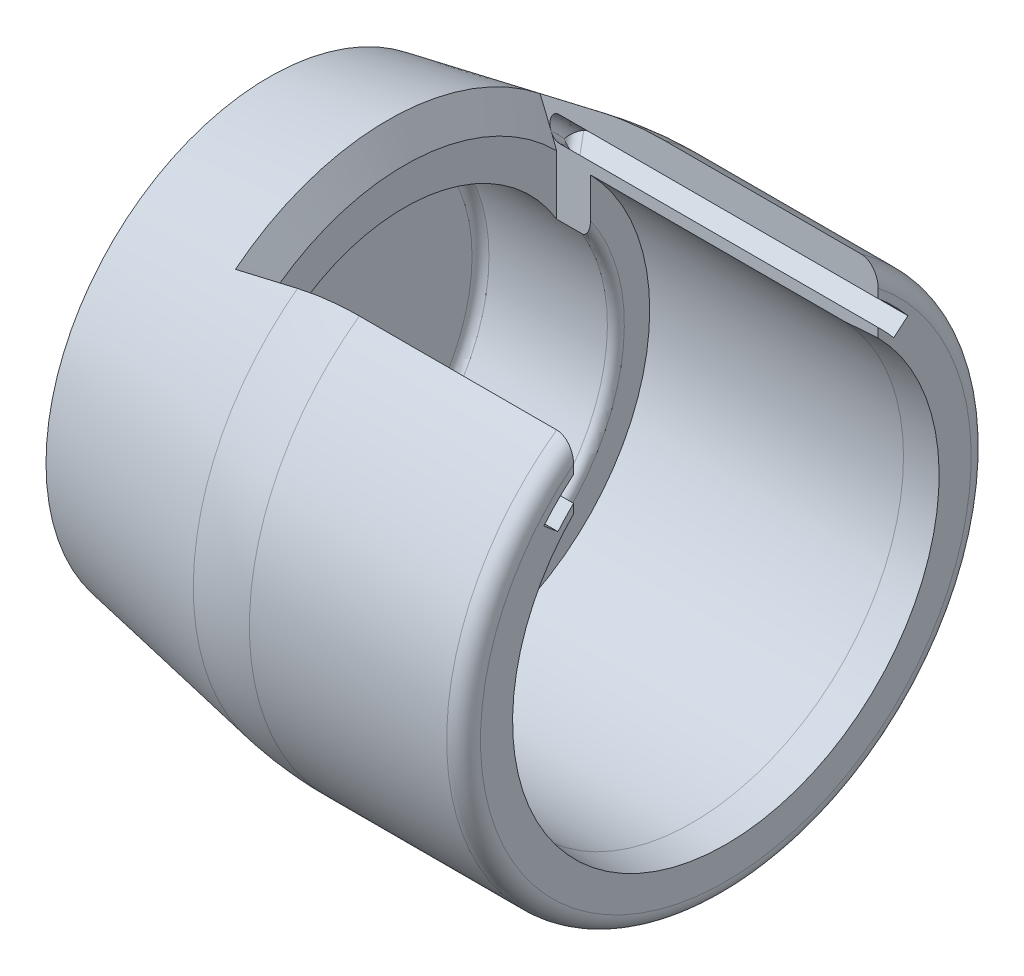
SolidWorks part; units mm, degrees
material "ABS"
ref_plane "Přední rovina" through (0, 0, 0) normal (0, 0, 1) x (1, 0, 0)
ref_plane "Horní rovina" through (0, 0, 0) normal (0, 1, 0) x (1, 0, 0)
ref_plane "Pravá rovina" through (0, 0, 0) normal (1, 0, 0) x (0, 0, -1)
sketch "Skica1" plane through (0, 0, 0) normal (0, 0, 1) x (1, 0, 0)
  line L0 (-22.0025, 0) -> (25.5285, 0) construction
  line L1 (-18.0063, 0) -> (-18.0063, 15.5)
  line L2 (-18.0063, 15.5) -> (8.9937, 15.5)
  line L3 (9.9937, 14.5) -> (9.9937, 12.5)
  line L4 (9.9937, 12.5) -> (-7.0063, 12.5)
  line L5 (-15.0063, 10.5) -> (-15.0063, 0)
  line L6 (-15.0063, 0) -> (-18.0063, 0)
  line L7 (-18.0063, 12.9944) -> (-4.5063, 15.5)
  line L10 (-15.0063, 10.5) -> (-7.0063, 10.5)
  line L11 (-7.0063, 12.5) -> (-7.0063, 10.5)
  line L12 (7.9937, 12.5) -> (9.9937, 12.6048)
  line L13 (-17.0063, 0) -> (-17.0063, 15.5)
  arc A0 (8.9937, 15.5) -> (9.9937, 14.5) centre (8.9937, 14.5) cw
  dimension "D1" = 12.5
  dimension "D2" = 3
  dimension "D3" = 3
  dimension "D8" = 1
  dimension "D4" = 25
  dimension "D5" = 8
  dimension "D6" = 2
  dimension "D7" = 3
  dimension "D9" = 3
  dimension "D10" = 2
  dimension "D11" = 1
revolve "Rotovat1" add sketch "Skica1" angle 360 about L0 region at (-16.695, 6.59, 0)
fillet "Zaoblit2" radius 0.5 2 edges at (-7.0063, 0, 10.5) (-15.0063, 0, 10.5)
sketch "Skica2" plane through (9.9937, 0, 0) normal (1, 0, 0) x (0, 0, -1)
  line L0 (-9.9203, 8.3741) -> (-10.7629, 9.0812)
  line L1 (-9, 17) -> (9, 17)
  line L2 (-9, 17) -> (-9, 10.839)
  line L3 (-9, 0.05) -> (9, 0.05)
  line L4 (9, 17) -> (9, 10.839)
  line L6 (10.7629, 9.0812) -> (9.9203, 8.3741)
  line L7 (-10.7629, 9.0812) -> (0, 0.05) construction
  line L8 (0, 0.05) -> (10.7629, 9.0812) construction
  line L9 (0, 0.05) -> (0, 17) construction
  line L10 (-9, 9.3614) -> (-9, 0.05)
  line L11 (9, 9.3614) -> (9, 0.05)
  arc A0 (-9, 9.3614) -> (-9.9203, 8.3741) centre (0, 0.05) ccw
  arc A1 (10.7629, 9.0812) -> (9, 10.839) centre (0, 0.05) ccw
  arc A2 (9.9203, 8.3741) -> (9, 9.3614) centre (0, 0.05) ccw
  circle A3 centre (0, 0) radius 14.5 construction
  arc A4 (-9, 10.839) -> (-10.7629, 9.0812) centre (0, 0.05) ccw
  point P4 (0, 17)
  dimension "D4" = 1.1
  dimension "D5" = 0.4
  dimension "D8" = 14.05
  dimension "D1" = 0
  dimension "D2" = 18
  dimension "D3" = 17
  dimension "D6" = 50
  dimension "D7" = 50
extrude "Odebrat vysunutím1" cut sketch "Skica2" against normal blind 19
chamfer "Zkosení1" distance 2 distance2 1 1 edges at (-9.0063, 14.6648, 0) first distance on face at (-9.0063, 9.7971, 0)
fillet "Zaoblit3" radius 0.55 6 edges
fillet "Zaoblit4" radius 20 1 edges at (-4.5063, -15.5, 0)
